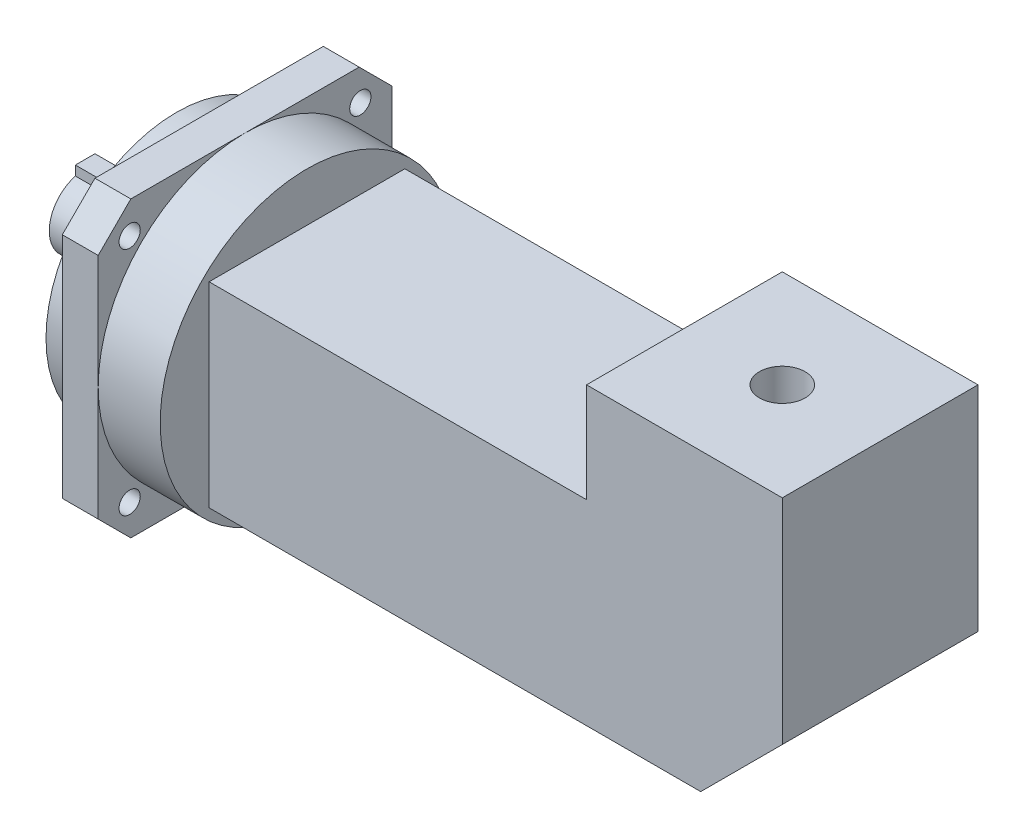
SolidWorks part; units mm, degrees
ref_plane "Front Plane" through (0, 0, 0) normal (0, 0, 1) x (1, 0, 0)
ref_plane "Top Plane" through (0, 0, 0) normal (0, 1, 0) x (1, 0, 0)
ref_plane "Right Plane" through (0, 0, 0) normal (1, 0, 0) x (0, 0, -1)
sketch "Sketch1" plane through (0, 0, 0) normal (1, 0, 0) x (0, 0, -1)
  line L1 (3, 13.5) -> (-3, 13.5)
  line L2 (3, 13.5) -> (3, 8.5)
  line L3 (3, 8.5) -> (-3, 8.5)
  line L4 (-3, 13.5) -> (-3, 8.5)
  line L5 (3, 13.5) -> (-3, 8.5) construction
  line L6 (3, 8.5) -> (-3, 13.5) construction
  circle A0 centre (0, 0) radius 40
  circle A1 centre (0, 0) radius 45
  circle A2 centre (0, 0) radius 11
  point P5 (0, 11)
  dimension "D1" = 90
  dimension "D4" = 22
  dimension "D5" = 80
  dimension "D2" = 6
  dimension "D3" = 5
extrude "Boss-Extrude1" add sketch "Sketch1" against normal blind 38 and the other way blind 10 contours L4 A2 L2 L3 | A2 L2 L1 L4 | L2 A2 L4 L3 region at (0, 12.1781, 0) region at (0, -0.375, 0) region at (0, 9.6843, 0)
extrude "Boss-Extrude2" add sketch "Sketch1<3>" against normal blind 10 contours A0 A2 L4 L1 L2 region at (0, 0, 38.8686)
sketch "Sketch1<3>" plane through (0, 0, 0) normal (1, 0, 0) x (0, 0, -1) same geometry as "Sketch1"
extrude "Boss-Extrude3" add sketch "Sketch1<4>" along normal blind 9 separate body contours A1 A0 | A0 A2 L4 L1 L2 | A2 L2 L1 L4 region at (0, 12.1781, 0) region at (0, 0, 38.8686) region at (0, 0, 43.7272)
sketch "Sketch1<4>" plane through (0, 0, 0) normal (1, 0, 0) x (0, 0, -1) same geometry as "Sketch1"
ref_plane "Plane1" through (9, 0, 0) normal (1, 0, 0) x (0, 0, -1)
sketch "Sketch2" plane through (0, 0, 0) normal (1, 0, 0) x (0, 0, -1)
  line L1 (-30, 30) -> (30, 30)
  line L2 (-30, 30) -> (-30, -30)
  line L3 (-30, -30) -> (30, -30)
  line L4 (30, 30) -> (30, -30)
  line L5 (-30, 30) -> (30, -30) construction
  line L6 (-30, -30) -> (30, 30) construction
  circle A0 centre (0, 0) radius 45
  dimension "D3" = 90
  dimension "D1" = 60
  dimension "D2" = 60
extrude "Boss-Extrude4" add sketch "Sketch2" along normal blind 30
extrude "Boss-Extrude5" add sketch "Sketch2<3>" along normal blind 205.7 contours L4 L1 L2 L3 region at (0, 0, 0)
sketch "Sketch2<3>" plane through (0, 0, 0) normal (1, 0, 0) x (0, 0, -1) same geometry as "Sketch2"
sketch "Sketch3" plane through (0, 0, 0) normal (0, 1, 0) x (1, 0, 0)
  line L0 (0, 0) -> (129.2704, 0) construction
  line L1 (205.7, -30) -> (205.7, 30) construction
  line L3 (145.7, 30) -> (205.7, 30)
  line L4 (145.7, 30) -> (145.7, -30)
  line L5 (145.7, -30) -> (205.7, -30)
  line L6 (205.7, 30) -> (205.7, -30)
  line L7 (145.7, 30) -> (205.7, -30) construction
  line L8 (145.7, -30) -> (205.7, 30) construction
  circle A0 centre (175.7, 0) radius 7
  point P3 (205.7, 0)
  point P4 (175.7, 0)
  point P7 (175.7, 0)
  dimension "D1" = 30
extrude "Boss-Extrude6" add sketch "Sketch3" along normal blind 60.5
chamfer "Chamfer1" distance 25 angle 45 1 edges at (205.7, -30, 0)
sketch "Sketch6" plane through (0, 0, 0) normal (1, 0, 0) x (0, 0, -1)
  line L0 (35, 45) -> (45, 35)
  line L1 (-35, 45) -> (35, 45)
  line L2 (-45, 35) -> (-45, -35)
  line L3 (-35, -45) -> (35, -45)
  line L4 (45, 35) -> (45, -35)
  line L5 (-45, 45) -> (45, -45) construction
  line L6 (-45, -45) -> (45, 45) construction
  line L7 (-45, 35) -> (-35, 45)
  line L8 (-45, -35) -> (-35, -45)
  line L9 (45, -35) -> (35, -45)
  circle A0 centre (0, 0) radius 50
  point P1 (0, 0)
  dimension "D3" = 100
  dimension "D1" = 90
  dimension "D2" = 90
extrude "Boss-Extrude7" add sketch "Sketch6" along normal blind 11 contours A0 L4 L0 L1 | L4 A0 L1 L2 L3 | A0 L1 L7 L2 | A0 L2 L8 L3 | A0 L3 L9 L4 region at (0, 37.0609, -37.0609) region at (0, 0, 0) region at (0, 37.0609, 37.0609) region at (0, -37.0609, -37.0609) region at (0, -37.0609, 37.0609)
sketch "Sketch7" plane through (0, 0, 0) normal (1, 0, 0) x (0, 0, -1)
  line L0 (0, 0) -> (48.1059, 48.1059) construction
  line L1 (48.1059, 48.1059) -> (-53.2405, -53.2405) construction
  line L2 (-53.2405, -53.2405) -> (0, 0) construction
  line L3 (0, 0) -> (48.1059, -48.1059) construction
  line L4 (48.1059, -48.1059) -> (-51.7597, 51.7597) construction
  circle A0 centre (0, 0) radius 50
  circle A1 centre (35.3553, 35.3553) radius 3.25
  circle A2 centre (-35.3553, 35.3553) radius 3.25
  circle A3 centre (35.3553, -35.3553) radius 3.25
  circle A4 centre (-35.3553, -35.3553) radius 3.25
  point P3 (35.3553, 35.3553)
  point P8 (35.3553, -35.3553)
  point P9 (-35.3553, -35.3553)
  point P10 (-35.3553, 35.3553)
  dimension "D1" = 6.5
  dimension "D2" = 6.5
  dimension "D3" = 6.5
  dimension "D4" = 6.5
extrude "Cut-Extrude2" cut sketch "Sketch7" along normal blind 51 contours A0 A1 | A0 A1 | A0 A3 | A0 A3 | A0 A4 | A0 A4 | A0 A2 | A0 A2 region at (0, 34.3667, -34.3667) region at (0, 36.3171, -36.3171) region at (0, -36.3171, -36.3171) region at (0, -34.3667, -34.3667) region at (0, 34.3667, 34.3667) region at (0, 36.3171, 36.3171) region at (0, -36.3171, 36.3171) region at (0, -34.3667, 34.3667)
